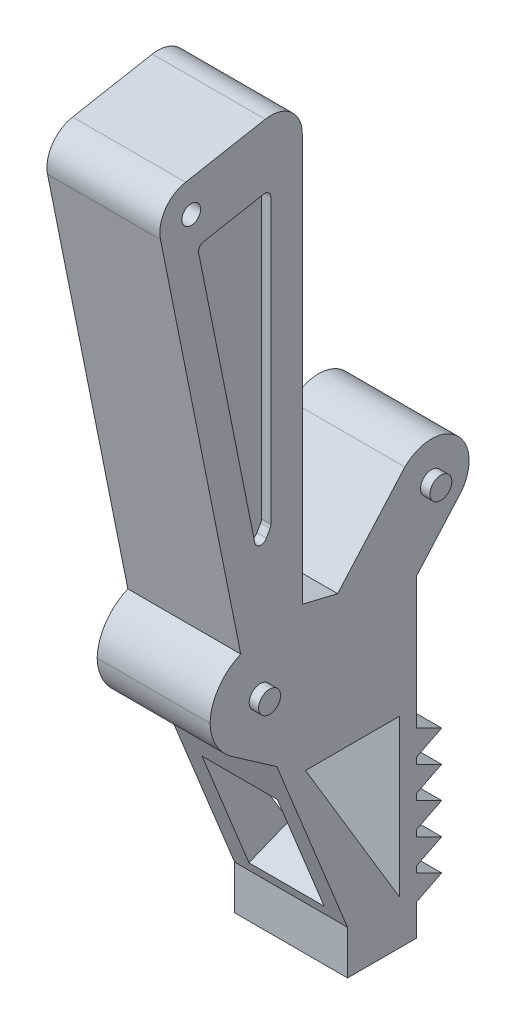
SolidWorks part; units mm, degrees
ref_plane "Front Plane" through (0, 0, 0) normal (0, 0, 1) x (1, 0, 0)
ref_plane "Top Plane" through (0, 0, 0) normal (0, 1, 0) x (1, 0, 0)
ref_plane "Right Plane" through (0, 0, 0) normal (1, 0, 0) x (0, 0, -1)
sketch "Sketch1" plane through (0, 0, 0) normal (1, 0, 0) x (0, 0, -1)
  line L8 (27.6465, -0.0095) -> (13.8469, 68.6168)
  line L9 (13.8469, 68.6168) -> (37.4503, 72.9618)
  line L10 (37.4503, 72.9618) -> (37.4503, 1.9618)
  line L11 (37.4503, 1.9618) -> (27.6465, -0.0095)
  line L12 (27.6465, -0.0095) -> (22.7446, -0.9952)
  line L13 (22.7446, -0.9952) -> (22.7446, -10.9952)
  line L14 (22.7446, -10.9952) -> (33.4055, -18.4348)
  line L15 (33.4055, -18.4348) -> (44.6714, -46.2391)
  line L16 (44.6714, -46.2391) -> (44.6714, -53.2391)
  line L17 (44.6714, -53.2391) -> (55.6714, -53.2391)
  line L18 (55.6714, -53.2391) -> (55.6714, -3.2391)
  line L19 (37.4503, 1.9618) -> (43.0947, 0.6109)
  line L20 (62.2889, 4.2582) -> (53.8036, 12.7435) construction
  line L21 (55.6714, -3.2391) -> (62.2889, 4.2582)
  line L22 (53.8036, 12.7435) -> (43.0947, 0.6109)
  arc A0 (62.2889, 4.2582) -> (53.3096, 12.1838) centre (58.0462, 8.5009) ccw
  dimension "D1" = 70
  dimension "D2" = 71
  dimension "D3" = 24
  dimension "D4" = 10
  dimension "D5" = 15
  dimension "D6" = 10
  dimension "D7" = 13
  dimension "D8" = 30
  dimension "D9" = 7
  dimension "D10" = 11
  dimension "D11" = 50
  dimension "D12" = 12
  dimension "D13" = 10
extrude "Boss-Extrude1" add sketch "Sketch1" along normal mid plane 18 contours L21 L20 L22 L19 L11 L12 L13 L14 L15 L16 L17 L18 | L11 L10 L9 L8 | L20 A0 region at (0, 40.6802, -28.6196) region at (0, -17.7486, -44.7256) region at (0, 10.3015, -59.8468)
sketch "Sketch3" plane through (9, 0, 0) normal (1, 0, 0) x (0, 0, -1)
  line L0 (52.9714, -46.2391) -> (52.9714, -21.2391)
  line L1 (52.9714, -21.2391) -> (37.9714, -21.2391)
  line L2 (37.9714, -21.2391) -> (52.9714, -46.2391)
  line L3 (44.6714, -46.2391) -> (53.256, -46.2391) construction
  line L4 (55.6714, -53.2391) -> (55.6714, -3.2391) construction
  dimension "D1" = 15
  dimension "D2" = 25
  dimension "D3" = 0
  dimension "D4" = 2.7
extrude "Cut-Extrude1" cut sketch "Sketch3" against normal blind 25
sketch "Sketch4" plane through (9, 0, 0) normal (1, 0, 0) x (0, 0, -1)
  line L0 (55.6714, -46.2391) -> (59.6714, -46.2391)
  line L1 (55.6714, -53.2391) -> (55.6714, -3.2391) construction
  line L2 (59.6714, -46.2391) -> (55.6714, -48.2391)
  line L3 (59.6714, -46.2391) -> (55.6714, -44.2391)
  line L4 (55.6714, -44.2391) -> (55.6714, -48.2391)
  line L5 (44.6714, -53.2391) -> (55.6714, -53.2391) construction
  line M18 (55.6714, -53.2391) -> (55.6714, -3.2391)
  dimension "D1" = 4
  dimension "D2" = 2
  dimension "D3" = 4
  dimension "D4" = 5
extrude "Boss-Extrude2" add sketch "Sketch4" against normal blind 18 contours L0 L3 M18 | L2 L0 M18 region at (9, -45.5724, -57.0047) region at (9, -46.9057, -57.0047)
pattern_linear "LPattern1" count 5 spacing 5 along (0, 1, 0) of "Boss-Extrude2"
fillet "Fillet1" radius 8 2 edges at (0, -10.9952, -22.7446) (0, -0.9952, -22.7446)
fillet "Fillet2" radius 5 2 edges at (0, 72.9618, -37.4503) (0, 68.6168, -13.8469)
sketch "Sketch5" plane through (9, 0, 0) normal (1, 0, 0) x (0, 0, -1)
  circle A0 centre (19.7507, 64.6196) radius 1.5
  dimension "D1" = 3
extrude "Cut-Extrude2" cut sketch "Sketch5" against normal blind 25
sketch "Sketch8" plane through (0, 9.0269, -22.2784) normal (0, -0.3755, 0.9268) x (1, 0, 0)
  line L0 (-9, -37.7975) -> (9, -37.7975) construction
  line L1 (-9, -29.6303) -> (-9, -59.6303) construction
  line L2 (9, -29.6303) -> (9, -59.6303) construction
  line L3 (0, -29.6303) -> (0, -59.6303) construction
  line L4 (9, -29.6303) -> (-9, -29.6303) construction
  line L5 (9, -59.6303) -> (-9, -59.6303) construction
  line L6 (-6, -37.7975) -> (6, -37.7975)
  line L7 (6, -37.7975) -> (6, -57.7273)
  line L8 (6, -57.7273) -> (-6, -57.7273)
  line L9 (-6, -57.7273) -> (-6, -37.7975)
  dimension "D1" = 12
  dimension "D2" = 6
  dimension "D3" = 3
  dimension "D4" = 3
extrude "Cut-Extrude4" cut sketch "Sketch8" against normal blind 8
sketch "Sketch9" plane through (9, 0, 0) normal (1, 0, 0) x (0, 0, -1)
  circle A0 centre (58.0462, 8.5009) radius 1.75
  dimension "D1" = 3.5
extrude "Boss-Extrude3" add sketch "Sketch9" along normal blind 1.5
sketch "Sketch10" plane through (9, 0, 0) normal (1, 0, 0) x (0, 0, -1)
  circle A0 centre (30.7446, -7.3853) radius 1.75
  dimension "D1" = 3.5
extrude "Boss-Extrude4" add sketch "Sketch10" along normal blind 1.5
sketch "Sketch11" plane through (9, 0, 0) normal (1, 0, 0) x (0, 0, -1)
  line L26 (32.4503, 60.6725) -> (32.4503, 15.5091)
  line L27 (37.4503, 66.9574) -> (37.4503, 1.9618) construction
  line L28 (20.9369, 58.7205) -> (29.88, 14.2463)
  line L29 (27.6465, -0.0095) -> (14.8489, 63.6339) construction
  line L30 (21.7363, 59.9011) -> (31.2692, 61.656)
  line L31 (18.8455, 69.5369) -> (31.545, 71.8748) construction
  line L32 (32.3252, 15.0248) -> (31.7353, 13.9591)
  arc A5 (32.4503, 60.6725) -> (31.2692, 61.656) centre (31.4503, 60.6725) ccw
  arc A6 (20.9369, 58.7205) -> (21.7363, 59.9011) centre (21.9173, 58.9176) cw
  arc A7 (32.4503, 15.5091) -> (32.3252, 15.0248) centre (31.4503, 15.5091) cw
  arc A8 (29.88, 14.2463) -> (31.7353, 13.9591) centre (30.8604, 14.4434) ccw
  dimension "D1" = 1
  dimension "D2" = 1
  dimension "D3" = 5
  dimension "D4" = 5
  dimension "D5" = 10
extrude "Cut-Extrude6" cut sketch "Sketch11" against normal blind 1.5
ref_plane "Plane1" through (0, 0, 0) normal (1, 0, 0) x (0, 0, -1)
mirror "Mirror1" about plane through (0, 0, 0) normal (1, 0, 0) of "Boss-Extrude3", "Boss-Extrude4", "Cut-Extrude6"
